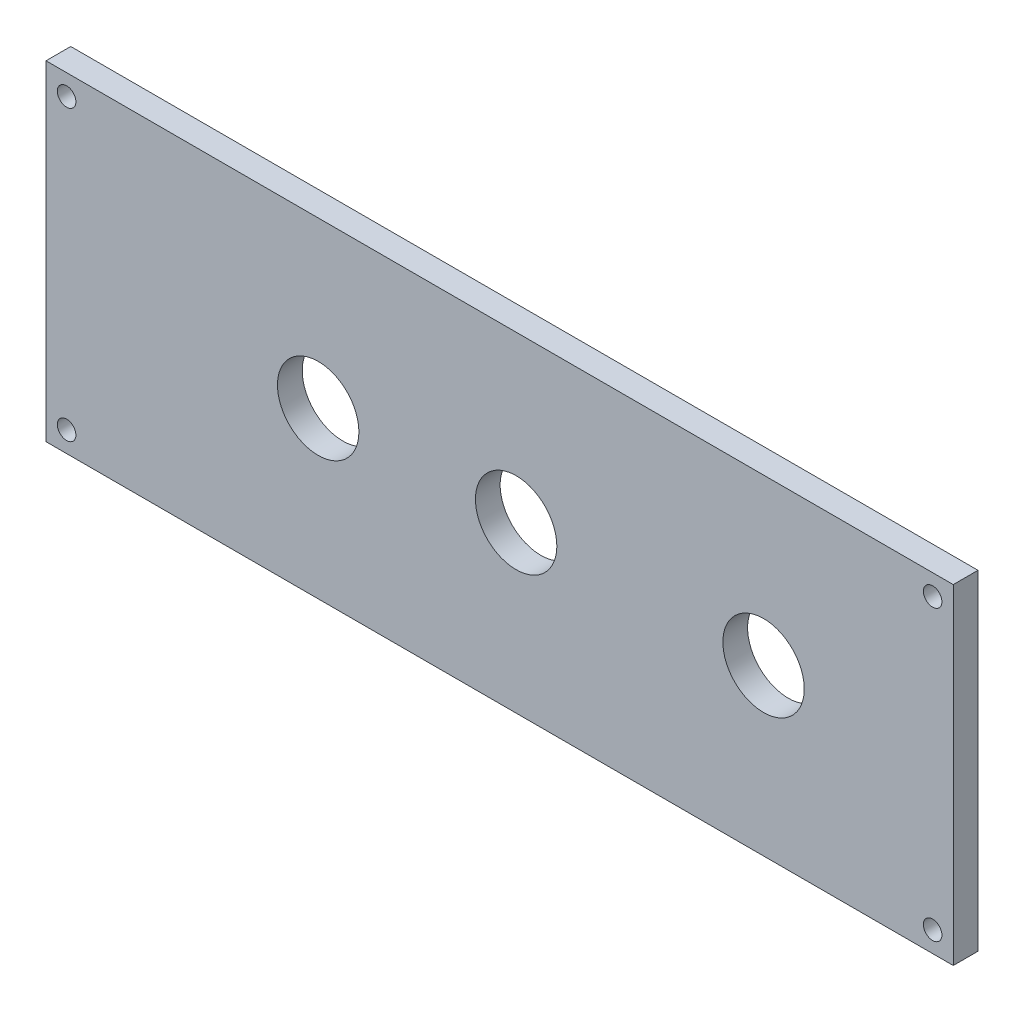
SolidWorks part; units mm, degrees
ref_plane "Front Plane" through (0, 0, 0) normal (0, 0, 1) x (1, 0, 0)
ref_plane "Top Plane" through (0, 0, 0) normal (0, 1, 0) x (1, 0, 0)
ref_plane "Right Plane" through (0, 0, 0) normal (1, 0, 0) x (0, 0, -1)
sketch "Sketch1" plane through (0, 0, 0) normal (0, 0, 1) x (1, 0, 0)
  line L1 (0, 0) -> (110, 0)
  line L2 (0, 0) -> (0, 40)
  line L3 (0, 40) -> (110, 40)
  line L4 (110, 0) -> (110, 40)
  dimension "D1" = 110
  dimension "D2" = 40
extrude "Boss-Extrude1" add sketch "Sketch1" along normal blind 3 contours L3 L4 L1 L2
sketch "Sketch2" plane through (0, 0, 3) normal (0, 0, 1) x (1, 0, 0)
  line L0 (0, 20) -> (110, 20) construction
  line L1 (0, 0) -> (0, 40) construction
  line L2 (110, 0) -> (110, 40) construction
  line L3 (0, 40) -> (110, 40) construction
  line L4 (55, 40) -> (55, 0) construction
  line L5 (0, 0) -> (110, 0) construction
  line L6 (48.175, 16) -> (48.175, 8)
  line L7 (45, 32) -> (48.175, 32)
  line L8 (45, 32) -> (45, 24)
  line L9 (45, 24) -> (48.175, 24)
  line L10 (48.175, 32) -> (48.175, 24)
  line L11 (45, 8) -> (48.175, 8)
  line L12 (45, 16) -> (45, 8)
  line L13 (45, 16) -> (48.175, 16)
  line L14 (48.175, 32) -> (48.175, 16) construction
  circle A1 centre (33, 20) radius 4.9365
  circle A2 centre (57, 20) radius 4.9365
  circle A3 centre (2.5, 37.5) radius 1.125
  circle A4 centre (107.5, 37.5) radius 1.125
  circle A5 centre (107.5, 2.5) radius 1.125
  circle A6 centre (2.5, 2.5) radius 1.125
  circle A7 centre (87, 20) radius 4.935
  dimension "D1" = 33
  dimension "D2" = 9.873
  dimension "D3" = 9.873
  dimension "D7" = 2.25
  dimension "D15" = 9.87
  dimension "D4" = 3.175
  dimension "D5" = 8
  dimension "D6" = 24
  dimension "D8" = 2.5
  dimension "D9" = 2.5
  dimension "D10" = 12
  dimension "D11" = 16
  dimension "D13" = 16
  dimension "D14" = 30
  dimension "D12" = 2
extrude "Cut-Extrude1" cut sketch "Sketch2" against normal through all contours A3 | A6 | A1 | A2 | A4 | A5 | A7 region at (33, 20, 3) region at (57, 20, 3) region at (2.5, 37.5, 3) region at (107.5, 37.5, 3) region at (107.5, 2.5, 3) region at (2.5, 2.5, 3) region at (87, 20, 3)
